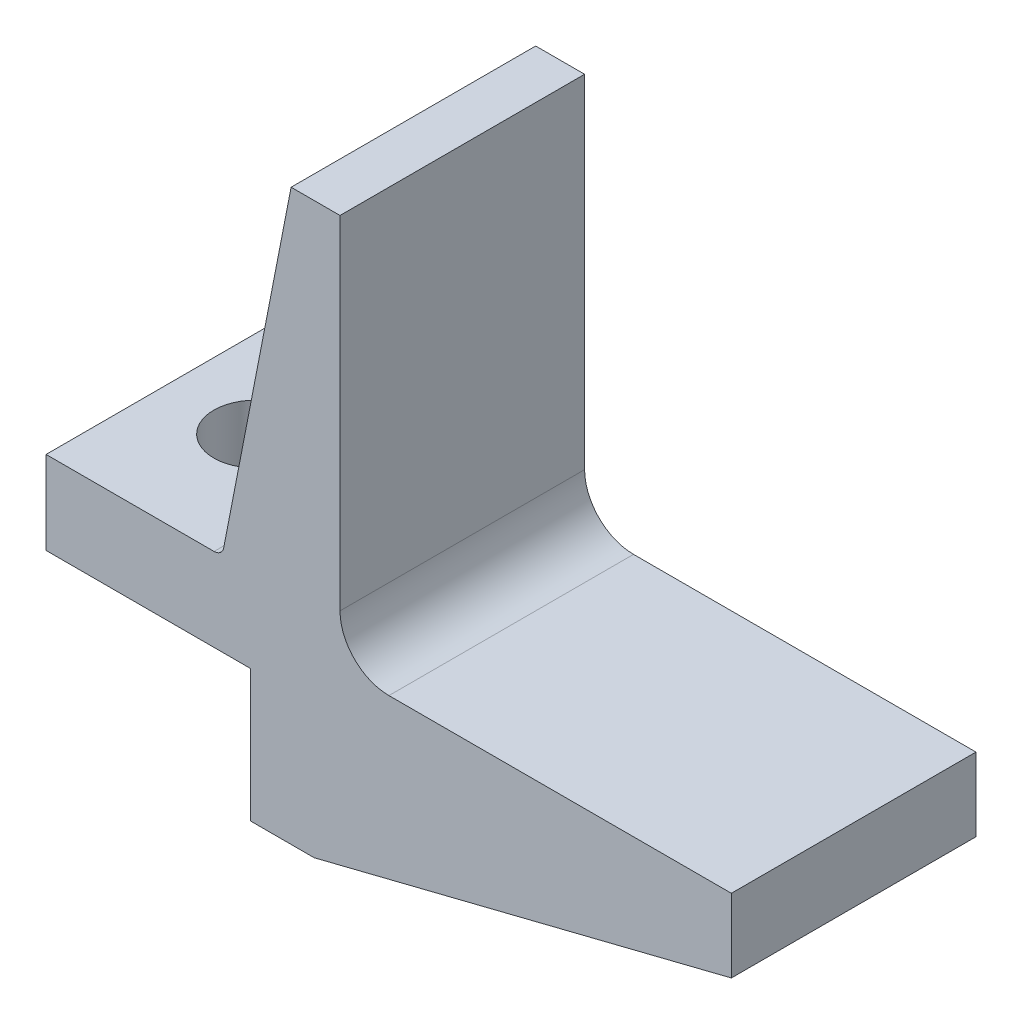
SolidWorks part; units mm, degrees
other "Markup1"
sketch "Sketch7" plane through (-38.1608, 50.8, 31.75) normal (-0.1424, 0.1459, 0.979) x (0.9898, 0.0098, 0.1425)
material "7075-T6 (SN)"
ref_plane "Front Plane" through (0, 0, 0) normal (0, 0, 1) x (1, 0, 0)
ref_plane "Top Plane" through (0, 0, 0) normal (0, 1, 0) x (1, 0, 0)
ref_plane "Right Plane" through (0, 0, 0) normal (1, 0, 0) x (0, 0, -1)
sketch "Sketch1" plane through (0, 0, 0) normal (0, 0, 1) x (1, 0, 0)
  line L0 (0, 0) -> (50.8, 0)
  line L1 (50.8, 0) -> (50.8, -9.525)
  line L2 (-11.6178, -5.9413) -> (-38.1608, -5.9413)
  line L3 (-38.1608, -5.9413) -> (-38.1608, 4.8537)
  line L4 (-38.1608, 4.8537) -> (-15.3008, 4.8537)
  line L5 (-15.3008, 4.8537) -> (-6.35, 50.8)
  line L6 (-6.35, 50.8) -> (0, 50.8)
  line L7 (0, 50.8) -> (0, 0)
  line L8 (-11.6178, -5.9413) -> (-11.6178, -23.0863)
  line L9 (-11.6178, -23.0863) -> (-3.3628, -23.0863)
  line L10 (-3.3628, -23.0863) -> (50.8, -9.525)
  dimension "D1" = 50.8
  dimension "D2" = 50.8
  dimension "D3" = 9.525
  dimension "D4" = 38.1608
  dimension "D5" = 6.35
  dimension "D6" = 22.86
  dimension "D7" = 26.543
  dimension "D8" = 10.795
  dimension "D9" = 17.145
  dimension "D10" = 8.255
  dimension "D11" = 4.8537
extrude "Boss-Extrude1" add sketch "Sketch1" along normal blind 31.75
hole_wizard "3/8 (0.375) Diameter Hole1" positions "Sketch8" profile "Sketch3" hole size "3/8" standard "ANSI Inch" end condition through all
sketch "Sketch8" plane through (0, 4.8537, 0) normal (0, 1, 0) x (1, 0, 0)
  line L1 (-38.1608, -31.75) -> (-38.1608, 0) construction
  point P0 (-26.8578, -15.875)
  point P8 (-38.1608, -15.875)
  dimension "D1" = 11.303
sketch "Sketch3" plane through (-26.8578, 4.8537, 15.875) normal (1, 0, 0) x (0, 0, 1)
  line L0 (0, 0) -> (0, 27.94)
  line L1 (0, 27.94) -> (5.3975, 27.94)
  line L2 (5.3975, 27.94) -> (5.3975, 0)
  line L5 (5.3975, 0) -> (0, 0)
  line L11 (0, -6.35) -> (0, 107.95) construction
  dimension "Thru Hole Dia." = 10.795
  dimension "Thru Hole Depth" = 27.94
fillet "Fillet1" radius 1.27 1 edges at (-15.3008, 4.8537, 15.875)
fillet "Fillet2" radius 6.35 1 edges at (0, 0, 15.875)
chamfer "Chamfer1" [suppressed] distance 0.254 angle 45
